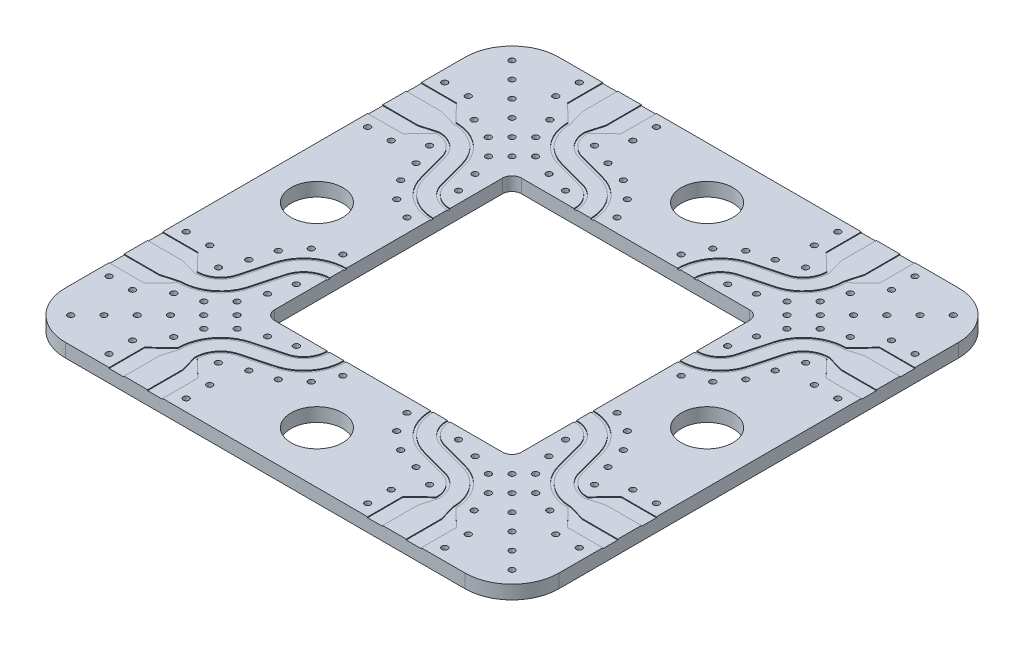
SolidWorks part; units mm, degrees
material "Custom Plastic"
ref_plane "Front Plane" through (0, 0, 0) normal (0, 0, 1) x (1, 0, 0)
ref_plane "Top Plane" through (0, 0, 0) normal (0, 1, 0) x (1, 0, 0)
ref_plane "Right Plane" through (0, 0, 0) normal (1, 0, 0) x (0, 0, -1)
sketch "Sketch1" plane through (0, 0, 0) normal (0, 1, 0) x (1, 0, 0)
  line L5 (-10.5, 10.5) -> (10.5, 10.5)
  line L6 (-10.5, 10.5) -> (-10.5, -10.5)
  line L7 (-10.5, -10.5) -> (10.5, -10.5)
  line L8 (10.5, 10.5) -> (10.5, -10.5)
  line L9 (-10.5, 10.5) -> (10.5, -10.5) construction
  line L10 (-10.5, -10.5) -> (10.5, 10.5) construction
  point P0 (0, 0)
  dimension "D1" = 21
extrude "Boss-Extrude1" add sketch "Sketch1" along normal blind 0.58
sketch "Sketch2" plane through (0, 0.58, 0) normal (0, 1, 0) x (1, 0, 0)
  line L5 (-5.25, 5.25) -> (5.25, 5.25)
  line L6 (-5.25, 5.25) -> (-5.25, -5.25)
  line L7 (-5.25, -5.25) -> (5.25, -5.25)
  line L8 (5.25, 5.25) -> (5.25, -5.25)
  line L9 (-5.25, 5.25) -> (5.25, -5.25) construction
  line L10 (-5.25, -5.25) -> (5.25, 5.25) construction
  point P0 (0, 0)
  dimension "D1" = 10.5
extrude "Cut-Extrude1" cut sketch "Sketch2" against normal through all
fillet "Fillet1" radius 2 4 edges at (-10.5, 0.29, 10.5) (-10.5, 0.29, -10.5) (10.5, 0.29, -10.5) (10.5, 0.29, 10.5)
fillet "Fillet2" radius 0.4 4 edges at (-5.25, 0.29, 5.25) (5.25, 0.29, 5.25) (5.25, 0.29, -5.25) (-5.25, 0.29, -5.25)
sketch "Sketch3" plane through (0, 0.58, 0) normal (0, 1, 0) x (1, 0, 0)
  line L0 (-1000, 0) -> (49000, 0) construction
  line L1 (0, -1000) -> (0, 49000) construction
  line L2 (-1000.1511, 5.5) -> (48999.7528, 5.5) construction
  line L3 (-999.6259, -5.5) -> (49000.7521, -5.5) construction
  line L4 (-1006.7067, 2.2) -> (48970.3156, 2.2) construction
  line L5 (-995.6657, -2.2) -> (48999.0786, -2.2) construction
  line L8 (6.3218, 3.3211) -> (6.6489, 4.535)
  line L10 (5.25, 1.9) -> (5.25, 1.79)
  line L12 (7.2282, 4.3789) -> (6.9011, 3.165)
  line L43 (7.0073, 3.1364) -> (7.3345, 4.3502)
  line L45 (6.5427, 4.5636) -> (6.2155, 3.3498)
  line L48 (10.5, 6) -> (10.5, 5) construction
  line L49 (8.3, 5.91) -> (9, 6.64)
  line L137 (9, 6) -> (8.3, 5.8)
  line L138 (8.3, 5.2) -> (9, 5)
  line L140 (9, 4.36) -> (8.3, 5.09)
  line L141 (8.3, 5.8) -> (8.3, 5.2) construction
  line L224 (5.25, 2.5) -> (5.25, 1.9) construction
  line L312 (5.25, 2.61) -> (5.25, 2.5)
  line L314 (10.5, 6.64) -> (9, 6.64)
  line L315 (10.5, 6.64) -> (10.5, 6)
  line L316 (10.5, 6) -> (9, 6)
  line L319 (10.5, 5) -> (9, 5)
  line L320 (10.5, 5) -> (10.5, 4.36)
  line L321 (10.5, 4.36) -> (9, 4.36)
  line L433 (10.5, -8.5) -> (10.5, 8.5) construction
  line L434 (5.25, -4.85) -> (5.25, 4.85) construction
  line L435 (10.5, -5) -> (10.5, -4.36)
  line L436 (10.5, -5) -> (9, -5)
  line L437 (10.5, -4.36) -> (9, -4.36)
  line L438 (9, -4.36) -> (8.3, -5.09)
  line L439 (8.3, -5.2) -> (9, -5)
  line L440 (7.2282, -4.3789) -> (6.9011, -3.165)
  line L441 (7.0073, -3.1364) -> (7.3345, -4.3502)
  line L442 (5.25, -1.9) -> (5.25, -1.79)
  line L443 (5.25, -2.61) -> (5.25, -2.5)
  line L444 (6.5427, -4.5636) -> (6.2155, -3.3498)
  line L445 (6.3218, -3.3211) -> (6.6489, -4.535)
  line L446 (10.5, -6.64) -> (9, -6.64)
  line L447 (8.3, -5.91) -> (9, -6.64)
  line L448 (9, -6) -> (8.3, -5.8)
  line L449 (10.5, -6) -> (9, -6)
  line L450 (10.5, -6.64) -> (10.5, -6)
  line L451 (-5, -10.5) -> (-4.36, -10.5)
  line L452 (-5, -10.5) -> (-5, -9)
  line L453 (-4.36, -10.5) -> (-4.36, -9)
  line L454 (-4.36, -9) -> (-5.09, -8.3)
  line L455 (-5.2, -8.3) -> (-5, -9)
  line L456 (-4.3789, -7.2282) -> (-3.165, -6.9011)
  line L457 (-3.1364, -7.0073) -> (-4.3502, -7.3345)
  line L458 (-1.9, -5.25) -> (-1.79, -5.25)
  line L459 (-2.61, -5.25) -> (-2.5, -5.25)
  line L460 (-4.5636, -6.5427) -> (-3.3498, -6.2155)
  line L461 (-3.3211, -6.3218) -> (-4.535, -6.6489)
  line L462 (-6.64, -10.5) -> (-6.64, -9)
  line L463 (-5.91, -8.3) -> (-6.64, -9)
  line L464 (-6, -9) -> (-5.8, -8.3)
  line L465 (-6, -10.5) -> (-6, -9)
  line L466 (-6.64, -10.5) -> (-6, -10.5)
  line L467 (6.64, -10.5) -> (6, -10.5)
  line L468 (6.64, -10.5) -> (6.64, -9)
  line L469 (5.91, -8.3) -> (6.64, -9)
  line L470 (6, -9) -> (5.8, -8.3)
  line L471 (6, -10.5) -> (6, -9)
  line L472 (4.5636, -6.5427) -> (3.3498, -6.2155)
  line L473 (3.3211, -6.3218) -> (4.535, -6.6489)
  line L474 (2.61, -5.25) -> (2.5, -5.25)
  line L475 (1.9, -5.25) -> (1.79, -5.25)
  line L476 (4.3789, -7.2282) -> (3.165, -6.9011)
  line L477 (3.1364, -7.0073) -> (4.3502, -7.3345)
  line L478 (5.2, -8.3) -> (5, -9)
  line L479 (5, -10.5) -> (5, -9)
  line L480 (5, -10.5) -> (4.36, -10.5)
  line L481 (4.36, -10.5) -> (4.36, -9)
  line L482 (4.36, -9) -> (5.09, -8.3)
  line L483 (-10.5, 5) -> (-10.5, 4.36)
  line L484 (-10.5, 5) -> (-9, 5)
  line L485 (-10.5, 4.36) -> (-9, 4.36)
  line L486 (-9, 4.36) -> (-8.3, 5.09)
  line L487 (-8.3, 5.2) -> (-9, 5)
  line L488 (-7.2282, 4.3789) -> (-6.9011, 3.165)
  line L489 (-7.0073, 3.1364) -> (-7.3345, 4.3502)
  line L490 (-5.25, 1.9) -> (-5.25, 1.79)
  line L491 (-5.25, 2.61) -> (-5.25, 2.5)
  line L492 (-6.5427, 4.5636) -> (-6.2155, 3.3498)
  line L493 (-6.3218, 3.3211) -> (-6.6489, 4.535)
  line L494 (-10.5, 6.64) -> (-9, 6.64)
  line L495 (-8.3, 5.91) -> (-9, 6.64)
  line L496 (-9, 6) -> (-8.3, 5.8)
  line L497 (-10.5, 6) -> (-9, 6)
  line L498 (-10.5, 6.64) -> (-10.5, 6)
  line L499 (-10.5, -6.64) -> (-10.5, -6)
  line L500 (-10.5, -6.64) -> (-9, -6.64)
  line L501 (-8.3, -5.91) -> (-9, -6.64)
  line L502 (-9, -6) -> (-8.3, -5.8)
  line L503 (-10.5, -6) -> (-9, -6)
  line L504 (-6.5427, -4.5636) -> (-6.2155, -3.3498)
  line L505 (-6.3218, -3.3211) -> (-6.6489, -4.535)
  line L506 (-5.25, -2.61) -> (-5.25, -2.5)
  line L507 (-5.25, -1.9) -> (-5.25, -1.79)
  line L508 (-7.2282, -4.3789) -> (-6.9011, -3.165)
  line L509 (-7.0073, -3.1364) -> (-7.3345, -4.3502)
  line L510 (-8.3, -5.2) -> (-9, -5)
  line L511 (-10.5, -5) -> (-9, -5)
  line L512 (-10.5, -5) -> (-10.5, -4.36)
  line L513 (-10.5, -4.36) -> (-9, -4.36)
  line L514 (-9, -4.36) -> (-8.3, -5.09)
  line L515 (5, 10.5) -> (4.36, 10.5)
  line L516 (5, 10.5) -> (5, 9)
  line L517 (4.36, 10.5) -> (4.36, 9)
  line L518 (4.36, 9) -> (5.09, 8.3)
  line L519 (5.2, 8.3) -> (5, 9)
  line L520 (4.3789, 7.2282) -> (3.165, 6.9011)
  line L521 (3.1364, 7.0073) -> (4.3502, 7.3345)
  line L522 (1.9, 5.25) -> (1.79, 5.25)
  line L523 (2.61, 5.25) -> (2.5, 5.25)
  line L524 (4.5636, 6.5427) -> (3.3498, 6.2155)
  line L525 (3.3211, 6.3218) -> (4.535, 6.6489)
  line L526 (6.64, 10.5) -> (6.64, 9)
  line L527 (5.91, 8.3) -> (6.64, 9)
  line L528 (6, 9) -> (5.8, 8.3)
  line L529 (6, 10.5) -> (6, 9)
  line L530 (6.64, 10.5) -> (6, 10.5)
  line L531 (-6.64, 10.5) -> (-6, 10.5)
  line L532 (-6.64, 10.5) -> (-6.64, 9)
  line L533 (-5.91, 8.3) -> (-6.64, 9)
  line L534 (-6, 9) -> (-5.8, 8.3)
  line L535 (-6, 10.5) -> (-6, 9)
  line L536 (-4.5636, 6.5427) -> (-3.3498, 6.2155)
  line L537 (-3.3211, 6.3218) -> (-4.535, 6.6489)
  line L538 (-2.61, 5.25) -> (-2.5, 5.25)
  line L539 (-1.9, 5.25) -> (-1.79, 5.25)
  line L540 (-4.3789, 7.2282) -> (-3.165, 6.9011)
  line L541 (-3.1364, 7.0073) -> (-4.3502, 7.3345)
  line L542 (-5.2, 8.3) -> (-5, 9)
  line L543 (-5, 10.5) -> (-5, 9)
  line L544 (-5, 10.5) -> (-4.36, 10.5)
  line L545 (-4.36, 10.5) -> (-4.36, 9)
  line L546 (-4.36, 9) -> (-5.09, 8.3)
  arc A4 (8.3, 5.91) -> (6.5427, 4.5636) centre (8.3, 4.09) ccw
  arc A5 (8.3, 5.8) -> (6.6489, 4.535) centre (8.3, 4.09) ccw
  arc A6 (8.3, 5.2) -> (7.2282, 4.3789) centre (8.3, 4.09) ccw
  arc A7 (8.3, 5.09) -> (7.3345, 4.3502) centre (8.3, 4.09) ccw
  arc A36 (5.25, 1.79) -> (7.0073, 3.1364) centre (5.25, 3.61) ccw
  arc A37 (5.25, 1.9) -> (6.9011, 3.165) centre (5.25, 3.61) ccw
  arc A38 (5.25, 2.61) -> (6.2155, 3.3498) centre (5.25, 3.61) ccw
  arc A39 (5.25, 2.5) -> (6.3218, 3.3211) centre (5.25, 3.61) ccw
  arc A100 (8.3, -5.2) -> (7.2282, -4.3789) centre (8.3, -4.09) cw
  arc A101 (8.3, -5.09) -> (7.3345, -4.3502) centre (8.3, -4.09) cw
  arc A102 (5.25, -1.79) -> (7.0073, -3.1364) centre (5.25, -3.61) cw
  arc A103 (5.25, -1.9) -> (6.9011, -3.165) centre (5.25, -3.61) cw
  arc A104 (5.25, -2.61) -> (6.2155, -3.3498) centre (5.25, -3.61) cw
  arc A105 (5.25, -2.5) -> (6.3218, -3.3211) centre (5.25, -3.61) cw
  arc A106 (8.3, -5.8) -> (6.6489, -4.535) centre (8.3, -4.09) cw
  arc A107 (8.3, -5.91) -> (6.5427, -4.5636) centre (8.3, -4.09) cw
  arc A116 (-5.2, -8.3) -> (-4.3789, -7.2282) centre (-4.09, -8.3) cw
  arc A117 (-5.09, -8.3) -> (-4.3502, -7.3345) centre (-4.09, -8.3) cw
  arc A118 (-1.79, -5.25) -> (-3.1364, -7.0073) centre (-3.61, -5.25) cw
  arc A119 (-1.9, -5.25) -> (-3.165, -6.9011) centre (-3.61, -5.25) cw
  arc A120 (-2.61, -5.25) -> (-3.3498, -6.2155) centre (-3.61, -5.25) cw
  arc A121 (-2.5, -5.25) -> (-3.3211, -6.3218) centre (-3.61, -5.25) cw
  arc A122 (-5.8, -8.3) -> (-4.535, -6.6489) centre (-4.09, -8.3) cw
  arc A123 (-5.91, -8.3) -> (-4.5636, -6.5427) centre (-4.09, -8.3) cw
  arc A124 (5.91, -8.3) -> (4.5636, -6.5427) centre (4.09, -8.3) ccw
  arc A125 (5.8, -8.3) -> (4.535, -6.6489) centre (4.09, -8.3) ccw
  arc A126 (2.61, -5.25) -> (3.3498, -6.2155) centre (3.61, -5.25) ccw
  arc A127 (2.5, -5.25) -> (3.3211, -6.3218) centre (3.61, -5.25) ccw
  arc A128 (1.9, -5.25) -> (3.165, -6.9011) centre (3.61, -5.25) ccw
  arc A129 (1.79, -5.25) -> (3.1364, -7.0073) centre (3.61, -5.25) ccw
  arc A130 (5.2, -8.3) -> (4.3789, -7.2282) centre (4.09, -8.3) ccw
  arc A131 (5.09, -8.3) -> (4.3502, -7.3345) centre (4.09, -8.3) ccw
  arc A132 (-8.3, 5.2) -> (-7.2282, 4.3789) centre (-8.3, 4.09) cw
  arc A133 (-8.3, 5.09) -> (-7.3345, 4.3502) centre (-8.3, 4.09) cw
  arc A134 (-5.25, 1.79) -> (-7.0073, 3.1364) centre (-5.25, 3.61) cw
  arc A135 (-5.25, 1.9) -> (-6.9011, 3.165) centre (-5.25, 3.61) cw
  arc A136 (-5.25, 2.61) -> (-6.2155, 3.3498) centre (-5.25, 3.61) cw
  arc A137 (-5.25, 2.5) -> (-6.3218, 3.3211) centre (-5.25, 3.61) cw
  arc A138 (-8.3, 5.8) -> (-6.6489, 4.535) centre (-8.3, 4.09) cw
  arc A139 (-8.3, 5.91) -> (-6.5427, 4.5636) centre (-8.3, 4.09) cw
  arc A140 (-8.3, -5.91) -> (-6.5427, -4.5636) centre (-8.3, -4.09) ccw
  arc A141 (-8.3, -5.8) -> (-6.6489, -4.535) centre (-8.3, -4.09) ccw
  arc A142 (-5.25, -2.61) -> (-6.2155, -3.3498) centre (-5.25, -3.61) ccw
  arc A143 (-5.25, -2.5) -> (-6.3218, -3.3211) centre (-5.25, -3.61) ccw
  arc A144 (-5.25, -1.9) -> (-6.9011, -3.165) centre (-5.25, -3.61) ccw
  arc A145 (-5.25, -1.79) -> (-7.0073, -3.1364) centre (-5.25, -3.61) ccw
  arc A146 (-8.3, -5.2) -> (-7.2282, -4.3789) centre (-8.3, -4.09) ccw
  arc A147 (-8.3, -5.09) -> (-7.3345, -4.3502) centre (-8.3, -4.09) ccw
  arc A148 (5.2, 8.3) -> (4.3789, 7.2282) centre (4.09, 8.3) cw
  arc A149 (5.09, 8.3) -> (4.3502, 7.3345) centre (4.09, 8.3) cw
  arc A150 (1.79, 5.25) -> (3.1364, 7.0073) centre (3.61, 5.25) cw
  arc A151 (1.9, 5.25) -> (3.165, 6.9011) centre (3.61, 5.25) cw
  arc A152 (2.61, 5.25) -> (3.3498, 6.2155) centre (3.61, 5.25) cw
  arc A153 (2.5, 5.25) -> (3.3211, 6.3218) centre (3.61, 5.25) cw
  arc A154 (5.8, 8.3) -> (4.535, 6.6489) centre (4.09, 8.3) cw
  arc A155 (5.91, 8.3) -> (4.5636, 6.5427) centre (4.09, 8.3) cw
  arc A156 (-5.91, 8.3) -> (-4.5636, 6.5427) centre (-4.09, 8.3) ccw
  arc A157 (-5.8, 8.3) -> (-4.535, 6.6489) centre (-4.09, 8.3) ccw
  arc A158 (-2.61, 5.25) -> (-3.3498, 6.2155) centre (-3.61, 5.25) ccw
  arc A159 (-2.5, 5.25) -> (-3.3211, 6.3218) centre (-3.61, 5.25) ccw
  arc A160 (-1.9, 5.25) -> (-3.165, 6.9011) centre (-3.61, 5.25) ccw
  arc A161 (-1.79, 5.25) -> (-3.1364, 7.0073) centre (-3.61, 5.25) ccw
  arc A162 (-5.2, 8.3) -> (-4.3789, 7.2282) centre (-4.09, 8.3) ccw
  arc A163 (-5.09, 8.3) -> (-4.3502, 7.3345) centre (-4.09, 8.3) ccw
  point P19 (8.3, 5.5)
  point P20 (10.5, 5.5)
  point P24 (-3.6065, -7.7435)
  point P25 (-4.1065, -7.7435)
  point P59 (2.9086, 8.0024)
  point P62 (3.4086, 8.0024)
  point P165 (5.25, 2.2)
  point P238 (0, 0)
  dimension "D6" = 1
  dimension "D7" = 1
  dimension "D1" = 11
  dimension "D2" = 4.4
  dimension "D3" = 0.64
  dimension "D4" = 1
  dimension "D5" = 0.11
  dimension "D8" = 0.6
  dimension "D9" = 1.5
  dimension "D10" = 2.2
extrude "Cut-Extrude4" cut sketch "Sketch3" against normal blind 0.035
sketch "Sketch5" plane through (0, 0.58, 0) normal (0, 1, 0) x (1, 0, 0)
  line L1 (4.36, 10.5) -> (-4.36, 10.5) construction
  circle A0 centre (0, 8.3) radius 1.1
  circle A1 centre (0, 8.3) radius 1.85 construction
  circle A4 centre (8.3, 0) radius 1.1
  circle A6 centre (0, -8.3) radius 1.1
  circle A8 centre (-8.3, 0) radius 1.1
  point P28 (0, 0)
  dimension "D1" = 2.2
  dimension "D3" = 3.7
  dimension "D2" = 2.2
  dimension "D8" = 4
extrude "Cut-Extrude5" cut sketch "Sketch5" against normal through all
sketch "Sketch6" plane through (0, 0.58, 0) normal (0, 1, 0) x (1, 0, 0)
  line L0 (5.25, -1.79) -> (5.25, 1.79) construction
  line L1 (10.5, 5) -> (10.5, 4.36) construction
  line L2 (-201000.1511, 5.5) -> (248999.7528, 5.5) construction
  line L5 (8.3, 5.8) -> (8.3, 5.2) construction
  line L6 (10.5, 6) -> (10.5, 6.64) construction
  line L7 (-1000, 0) -> (49000, 0) construction
  line L8 (5.7328, 3.4799) -> (6.0599, 4.6937) construction
  line L9 (7.4901, 3.0063) -> (7.8172, 4.2201) construction
  line L10 (8.3, 6.41) -> (10.5, 6.41) construction
  line L12 (8.3, 4.59) -> (10.5, 4.59) construction
  line L14 (0, -1000) -> (0, 49000) construction
  line L16 (6.3218, 3.3211) -> (6.6489, 4.535) construction
  circle A161 centre (8, 4.49) radius 0.125
  circle A171 centre (10, 3.86) radius 0.125
  circle A256 centre (-10, 3.86) radius 0.125
  arc A257 (5.25, 3.11) -> (5.7328, 3.4799) centre (5.25, 3.61) ccw construction
  circle A265 centre (-9, 3.86) radius 0.125
  arc A374 (5.25, 1.29) -> (7.4901, 3.0063) centre (5.25, 3.61) ccw construction
  arc A375 (7.8172, 4.2201) -> (8.3, 4.59) centre (8.3, 4.09) cw construction
  arc A376 (6.0599, 4.6937) -> (8.3, 6.41) centre (8.3, 4.09) cw construction
  circle A377 centre (5.7237, 3.4499) radius 0.125
  circle A378 centre (5.8307, 1.3639) radius 0.125
  circle A379 centre (6.7222, 1.8169) radius 0.125
  circle A380 centre (7.3401, 2.6032) radius 0.125
  circle A381 centre (7.6387, 3.5576) radius 0.125
  circle A382 centre (6.3496, 5.3463) radius 0.125
  circle A383 centre (7.0596, 6.0505) radius 0.125
  circle A384 centre (8, 6.3905) radius 0.125
  circle A385 centre (9, 7.14) radius 0.125
  circle A386 centre (10, 7.14) radius 0.125
  circle A387 centre (9, 3.86) radius 0.125
  circle A388 centre (5.9849, 4.4152) radius 0.125
  circle A389 centre (-8, 4.49) radius 0.125
  circle A390 centre (-7.6387, 3.5576) radius 0.125
  circle A391 centre (-7.3401, 2.6032) radius 0.125
  circle A392 centre (-6.7222, 1.8169) radius 0.125
  circle A393 centre (-5.8307, 1.3639) radius 0.125
  circle A394 centre (-5.7237, 3.4499) radius 0.125
  circle A395 centre (-5.9849, 4.4152) radius 0.125
  circle A396 centre (-6.3496, 5.3463) radius 0.125
  circle A397 centre (-7.0596, 6.0505) radius 0.125
  circle A398 centre (-8, 6.3905) radius 0.125
  circle A399 centre (-9, 7.14) radius 0.125
  circle A400 centre (-10, 7.14) radius 0.125
  circle A401 centre (3.86, 10) radius 0.125
  circle A402 centre (3.86, 9) radius 0.125
  circle A403 centre (4.49, 8) radius 0.125
  circle A404 centre (3.5576, 7.6387) radius 0.125
  circle A405 centre (2.6032, 7.3401) radius 0.125
  circle A406 centre (1.8169, 6.7222) radius 0.125
  circle A407 centre (1.3639, 5.8307) radius 0.125
  circle A408 centre (3.4499, 5.7237) radius 0.125
  circle A409 centre (4.4152, 5.9849) radius 0.125
  circle A410 centre (5.3463, 6.3496) radius 0.125
  circle A411 centre (6.0505, 7.0596) radius 0.125
  circle A412 centre (6.3905, 8) radius 0.125
  circle A413 centre (7.14, 9) radius 0.125
  circle A414 centre (7.14, 10) radius 0.125
  circle A415 centre (7.14, -10) radius 0.125
  circle A416 centre (7.14, -9) radius 0.125
  circle A417 centre (6.3905, -8) radius 0.125
  circle A418 centre (6.0505, -7.0596) radius 0.125
  circle A419 centre (5.3463, -6.3496) radius 0.125
  circle A420 centre (4.4152, -5.9849) radius 0.125
  circle A421 centre (3.4499, -5.7237) radius 0.125
  circle A422 centre (1.3639, -5.8307) radius 0.125
  circle A423 centre (1.8169, -6.7222) radius 0.125
  circle A424 centre (2.6032, -7.3401) radius 0.125
  circle A425 centre (3.5576, -7.6387) radius 0.125
  circle A426 centre (4.49, -8) radius 0.125
  circle A427 centre (3.86, -9) radius 0.125
  circle A428 centre (3.86, -10) radius 0.125
  circle A429 centre (10, -3.86) radius 0.125
  circle A430 centre (9, -3.86) radius 0.125
  circle A431 centre (8, -4.49) radius 0.125
  circle A432 centre (7.6387, -3.5576) radius 0.125
  circle A433 centre (7.3401, -2.6032) radius 0.125
  circle A434 centre (6.7222, -1.8169) radius 0.125
  circle A435 centre (5.8307, -1.3639) radius 0.125
  circle A436 centre (5.7237, -3.4499) radius 0.125
  circle A437 centre (5.9849, -4.4152) radius 0.125
  circle A438 centre (6.3496, -5.3463) radius 0.125
  circle A439 centre (7.0596, -6.0505) radius 0.125
  circle A440 centre (8, -6.3905) radius 0.125
  circle A441 centre (9, -7.14) radius 0.125
  circle A442 centre (10, -7.14) radius 0.125
  circle A443 centre (-10, -7.14) radius 0.125
  circle A444 centre (-9, -7.14) radius 0.125
  circle A445 centre (-8, -6.3905) radius 0.125
  circle A446 centre (-7.0596, -6.0505) radius 0.125
  circle A447 centre (-6.3496, -5.3463) radius 0.125
  circle A448 centre (-5.9849, -4.4152) radius 0.125
  circle A449 centre (-5.7237, -3.4499) radius 0.125
  circle A450 centre (-5.8307, -1.3639) radius 0.125
  circle A451 centre (-6.7222, -1.8169) radius 0.125
  circle A452 centre (-7.3401, -2.6032) radius 0.125
  circle A453 centre (-7.6387, -3.5576) radius 0.125
  circle A454 centre (-8, -4.49) radius 0.125
  circle A455 centre (-9, -3.86) radius 0.125
  circle A456 centre (-10, -3.86) radius 0.125
  circle A457 centre (-3.86, -10) radius 0.125
  circle A458 centre (-3.86, -9) radius 0.125
  circle A459 centre (-4.49, -8) radius 0.125
  circle A460 centre (-3.5576, -7.6387) radius 0.125
  circle A461 centre (-2.6032, -7.3401) radius 0.125
  circle A462 centre (-1.8169, -6.7222) radius 0.125
  circle A463 centre (-1.3639, -5.8307) radius 0.125
  circle A464 centre (-3.4499, -5.7237) radius 0.125
  circle A465 centre (-4.4152, -5.9849) radius 0.125
  circle A466 centre (-5.3463, -6.3496) radius 0.125
  circle A467 centre (-6.0505, -7.0596) radius 0.125
  circle A468 centre (-6.3905, -8) radius 0.125
  circle A469 centre (-7.14, -9) radius 0.125
  circle A470 centre (-7.14, -10) radius 0.125
  circle A471 centre (-7.14, 10) radius 0.125
  circle A472 centre (-7.14, 9) radius 0.125
  circle A473 centre (-6.3905, 8) radius 0.125
  circle A474 centre (-6.0505, 7.0596) radius 0.125
  circle A475 centre (-5.3463, 6.3496) radius 0.125
  circle A476 centre (-4.4152, 5.9849) radius 0.125
  circle A477 centre (-3.4499, 5.7237) radius 0.125
  circle A478 centre (-1.3639, 5.8307) radius 0.125
  circle A479 centre (-1.8169, 6.7222) radius 0.125
  circle A480 centre (-2.6032, 7.3401) radius 0.125
  circle A481 centre (-3.5576, 7.6387) radius 0.125
  circle A482 centre (-4.49, 8) radius 0.125
  circle A483 centre (-3.86, 9) radius 0.125
  circle A484 centre (-3.86, 10) radius 0.125
  point P258 (0, 0)
  dimension "D30" = 0.25
  dimension "D31" = 0.25
  dimension "D32" = 0.25
  dimension "D33" = 0.25
  dimension "D34" = 0.25
  dimension "D35" = 0.25
  dimension "D36" = 0.25
  dimension "D37" = 0.25
  dimension "D38" = 0.25
  dimension "D39" = 0.25
  dimension "D40" = 0.25
  dimension "D46" = 0.25
  dimension "D8" = 0.25
  dimension "D11" = 0.25
  dimension "D42" = 1
  dimension "D44" = 1
  dimension "D45" = 1
  dimension "D47" = 1
  dimension "D48" = 1
  dimension "D5" = 1
  dimension "D6" = 1
  dimension "D7" = 1
  dimension "D9" = 1
  dimension "D12" = 1
  dimension "D10" = 1.64
  dimension "D14" = 1.64
  dimension "D2" = 0.91
  dimension "D13" = 0.91
  dimension "D16" = 0.3
  dimension "D15" = 0.5
extrude "Cut-Extrude6" cut sketch "Sketch6" against normal through all
sketch "Sketch7" plane through (0, 0.58, 0) normal (0, 1, 0) x (1, 0, 0)
  line L0 (-706.9575, -706.9575) -> (34643.6101, 34643.6101) construction
  line L2 (-1000, 0) -> (49000, 0) construction
  line L3 (5.25, 2.61) -> (5.25, 4.85) construction
  circle A0 centre (5.85, 5.85) radius 0.125
  circle A1 centre (6.5571, 6.5571) radius 0.125
  circle A2 centre (7.2642, 7.2642) radius 0.125
  circle A3 centre (7.9713, 7.9713) radius 0.125
  circle A4 centre (8.6784, 8.6784) radius 0.125
  circle A5 centre (9.3855, 9.3855) radius 0.125
  circle A7 centre (5.85, -5.85) radius 0.125
  circle A8 centre (6.5571, -6.5571) radius 0.125
  circle A9 centre (7.2642, -7.2642) radius 0.125
  circle A10 centre (7.9713, -7.9713) radius 0.125
  circle A11 centre (8.6784, -8.6784) radius 0.125
  circle A12 centre (9.3855, -9.3855) radius 0.125
  circle A14 centre (-5.85, -5.85) radius 0.125
  circle A15 centre (-6.5571, -6.5571) radius 0.125
  circle A16 centre (-7.2642, -7.2642) radius 0.125
  circle A17 centre (-7.9713, -7.9713) radius 0.125
  circle A18 centre (-8.6784, -8.6784) radius 0.125
  circle A19 centre (-9.3855, -9.3855) radius 0.125
  circle A21 centre (-5.85, 5.85) radius 0.125
  circle A22 centre (-6.5571, 6.5571) radius 0.125
  circle A23 centre (-7.2642, 7.2642) radius 0.125
  circle A24 centre (-7.9713, 7.9713) radius 0.125
  circle A25 centre (-8.6784, 8.6784) radius 0.125
  circle A26 centre (-9.3855, 9.3855) radius 0.125
  circle A28 centre (10.0926, 10.0926) radius 0.125 [skipped]
  point P66 (0, 0)
  dimension "D1" = 0.25
  dimension "D3" = 45
  dimension "D2" = 0.6
  dimension "D4" = 7
extrude "Cut-Extrude7" cut sketch "Sketch7" against normal through all
equation "\"chip_size\"= 10mm"
equation "\"hold_edge\"= 1mm"
equation "\"cavity_size\"= \"holder_size\" - 2 * 4"
equation "\"holder_size\"= 29"
equation "\"M2P5\"= 2.5"
equation "\"height_SMA\"= 7"
equation "\"tube_SMA\"= 4mm"
equation "\"separation_SMA\"= 11"
equation "\"M2P5\"=2.5"
equation "\"via\"= 0.25"
equation "\"via_space\"= 1"
equation "\"via_gap\"= 0.5"
equation "\"D30@Sketch6\"=\"via\""
equation "\"D31@Sketch6\"=\"via\""
equation "\"D32@Sketch6\"=\"via\""
equation "\"D33@Sketch6\"=\"via\""
equation "\"D34@Sketch6\"=\"via\""
equation "\"D35@Sketch6\"=\"via\""
equation "\"D36@Sketch6\"=\"via\""
equation "\"D37@Sketch6\"=\"via\""
equation "\"D38@Sketch6\"=\"via\""
equation "\"D39@Sketch6\"=\"via\""
equation "\"D40@Sketch6\"=\"via\""
equation "\"D42@Sketch6\"=\"via_space\""
equation "\"D44@Sketch6\"=\"via_space\""
equation "\"D45@Sketch6\"=\"via_space\""
equation "\"D46@Sketch6\"=\"via\""
equation "\"D47@Sketch6\"=\"via_space\""
equation "\"D48@Sketch6\"=\"via_space\""
equation "\"D5@Sketch6\"=\"via_space\""
equation "\"D6@Sketch6\"=\"via_space\""
equation "\"D7@Sketch6\"=\"via_space\""
equation "\"D8@Sketch6\"=\"via\""
equation "\"D9@Sketch6\"=\"via_space\""
equation "\"D11@Sketch6\"=\"via\""
equation "\"D12@Sketch6\"=\"via_space\""
equation "\"D1@Sketch7\"=\"via\""
equation "\"D1@Sketch1\"=\"cavity_size\""
equation "\"D1@Sketch2\"=\"chip_size\"+0.5"
equation "\"w1\"= 1"
equation "\"D4@Sketch3\"=\"w1\""
equation "\"s1\"=0.64"
equation "\"D3@Sketch3\"=\"s1\""
equation "\"w2\"=0.6"
equation "\"D8@Sketch3\"=\"w2\""
equation "\"s2\"=0.11"
equation "\"D5@Sketch3\"=\"s2\""
equation "\"PCB_thickness\"= 0.51"
equation "\"PCB_Cu_thickness\"= 0.035"
equation "\"D1@Boss-Extrude1\"=\"PCB_thickness\"+2*\"PCB_Cu_thickness\""
equation "\"D1@Cut-Extrude4\"=\"PCB_Cu_thickness\""
